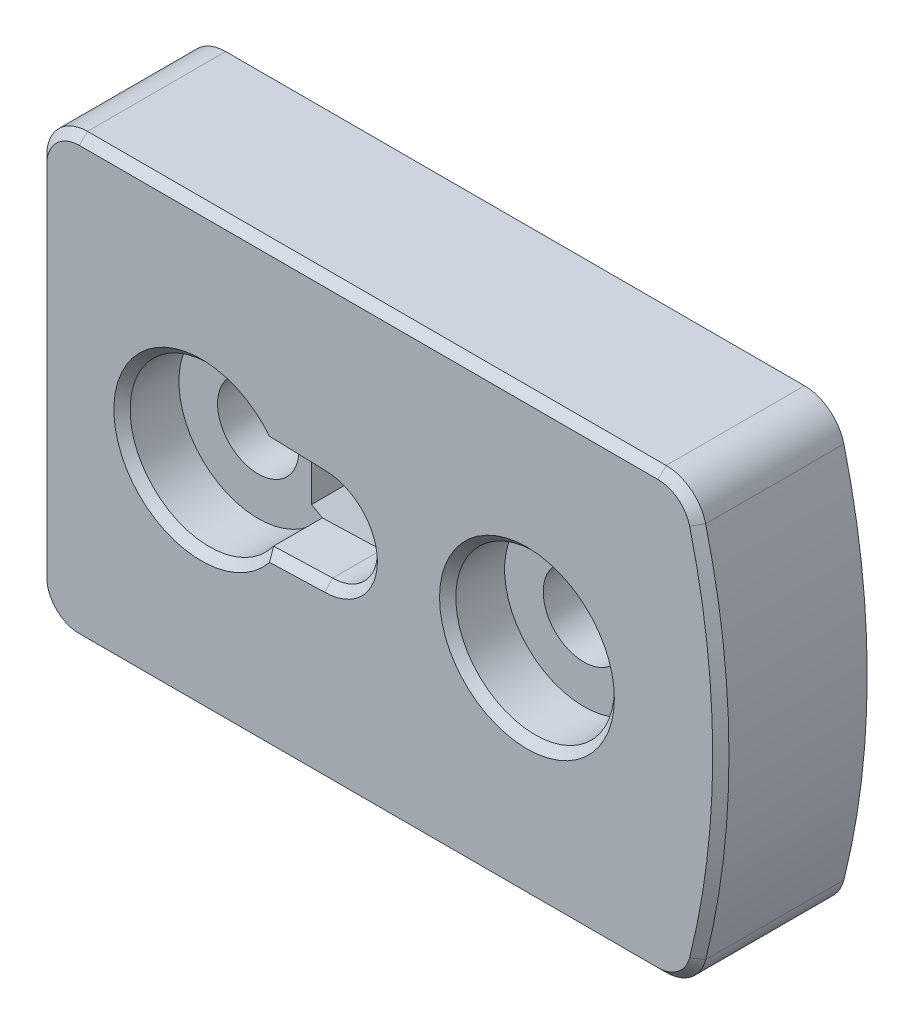
SolidWorks part; units mm, degrees
ref_plane "Front Plane" through (0, 0, 0) normal (0, 0, 1) x (1, 0, 0)
ref_plane "Top Plane" through (0, 0, 0) normal (0, 1, 0) x (1, 0, 0)
ref_plane "Right Plane" through (0, 0, 0) normal (1, 0, 0) x (0, 0, -1)
sketch "Sketch1" plane through (0, 0, 0) normal (0, 0, 1) x (1, 0, 0)
  line L0 (-10, 13.5) -> (-10, -13.5) construction
  line L1 (-20, -13.5) -> (20, -13.5)
  line L2 (-20, -13.5) -> (-20, 13.5)
  line L3 (-20, 13.5) -> (20, 13.5)
  line L5 (-20, -13.5) -> (20, 13.5) construction
  line L6 (-20, 13.5) -> (20, -13.5) construction
  line L7 (10.0266, 13.5) -> (10.0266, -13.5) construction
  line L8 (-8.92, 0) -> (-8.92, -38.6748) construction
  line L13 (-8.92, -38.6748) -> (-10.28, -38.6748) construction
  line L14 (-10.28, -38.6748) -> (-10.28, 0) construction
  line L15 (-2.42, 6.5) -> (43.4398, 6.5) construction
  line L16 (43.4398, 6.5) -> (43.4398, 7.86) construction
  line L17 (43.4398, 7.86) -> (-2.42, 7.86) construction
  line L18 (20, -13.5) -> (19.9199, -28.5934)
  circle A0 centre (-2.42, 0) radius 6.5
  arc A1 (-10.28, 0) -> (-2.42, 7.86) centre (-2.42, 0) cw construction
  arc A2 (20, 13.5) -> (20, -13.5) centre (-25.7558, 0) cw
  point P0 (-2.4466, -2.4466)
  point P7 (21.95, 0)
  dimension "D3" = 13
  dimension "D6" = 1.36
  dimension "D8" = 17.58
  dimension "D9" = 1.95
  dimension "D1" = 5.64
  dimension "D2" = 40
  dimension "D4" = 10
  dimension "D5" = 27
  dimension "D7" = 1.36
extrude "Boss-Extrude1" add sketch "Sketch1" along normal blind 9 contours L1 L3 L2 A0 | A0 region at (-19.5011, 0, 0) region at (-2.42, 0, 0)
sketch "Sketch2" plane through (0, 0, 9) normal (0, 0, 1) x (1, 0, 0)
  line L0 (-10, 13.5) -> (-10, -13.5) construction
  line L1 (10.0266, 13.5) -> (10.0266, -13.5) construction
  circle A0 centre (-10, 0) radius 2.5
  circle A1 centre (10.0266, 0) radius 2.5
  dimension "D1" = 5
extrude "Cut-Extrude1" cut sketch "Sketch2" against normal through all
sketch "Sketch3" plane through (0, 0, 9) normal (0, 0, 1) x (1, 0, 0)
  line L0 (-10, 13.5) -> (-10, -13.5) construction
  line L1 (10.0266, 13.5) -> (10.0266, -13.5) construction
  circle A0 centre (-10, 0) radius 4.875
  circle A1 centre (10.0266, 0) radius 4.875
  dimension "D1" = 9.75
extrude "Cut-Extrude2" cut sketch "Sketch3" against normal offset from surface (3.5 mm away) 5.5 up to face at (-7.5, 0, 0)
sketch "Sketch4" plane through (0, 0, 9) normal (0, 0, 1) x (1, 0, 0)
  circle A0 centre (-2.42, 0) radius 2.75
  dimension "D1" = 5.5
extrude "Cut-Extrude3" cut sketch "Sketch4" against normal through all
sketch "Sketch5" plane through (0, 0, 0) normal (0, 0, -1) x (-1, 0, 0)
  line L1 (6.72, -2.4826) -> (6.72, 2.4826)
  line L2 (6.72, 2.4826) -> (2.42, 4.9652)
  line L3 (2.42, 4.9652) -> (-1.88, 2.4826)
  line L4 (-1.88, 2.4826) -> (-1.88, -2.4826)
  line L5 (-1.88, -2.4826) -> (2.42, -4.9652)
  line L6 (2.42, -4.9652) -> (6.72, -2.4826)
  line L7 (20, -13.5) -> (20, 13.5) construction
  circle A0 centre (2.42, 0) radius 4.3 construction
  point P1 (2.42, 4.9652)
  dimension "D1" = 8.6
extrude "Cut-Extrude4" cut sketch "Sketch5" against normal up to surface (5.5 mm away) up to face at (-10.0225, 0, 5.5)
fillet "Fillet1" radius 2.5 4 edges at (-20, -13.5, 4.5) (-20, 13.5, 4.5) (20, -13.5, 4.5) (20, 13.5, 4.5)
chamfer "Chamfer1" distance 0.5 angle 45 8 edges at (0.2956, -13.5, 9) (-19.2678, -12.7678, 9) (-20, 0, 9) (-19.2678, 12.7678, 9) (0.2956, 13.5, 9) (19.629, -12.9711, 9) (21.95, 0, 9) (19.629, 12.9711, 9)
sketch "Sketch6" plane through (0, 0, 9) normal (0, 0, 1) x (1, 0, 0)
  line L5 (-6.0563, 2.8658) -> (-2.42, 2.75)
  line L6 (-6.0563, -2.8658) -> (-2.42, -2.75)
  line L7 (-6.0563, 2.8658) -> (-2.42, 4.9652) construction
  line L9 (-6.0563, -2.8658) -> (-6.72, -2.4826)
  line L12 (-6.72, 2.4826) -> (-2.42, 4.9652) construction
  line L13 (-6.72, -2.4826) -> (-6.72, 2.4826)
  line L19 (-6.72, 2.4826) -> (-6.0563, 2.8658)
  arc A0 (-5.1412, -0.397) -> (-5.1412, 0.397) centre (-2.42, 0) ccw construction
  arc A1 (-6.0563, 2.8658) -> (-6.0563, -2.8658) centre (-10, 0) ccw construction
  arc A2 (-2.42, -2.75) -> (-2.42, 2.75) centre (-2.42, 0) ccw
  arc A4 (-5.1412, 0.397) -> (-5.1412, -0.397) centre (-10, 0) ccw construction
  point P10 (-2.42, -2.75)
  point P11 (-1.6646, -2.6442)
  point P14 (-6.0521, 2.8682)
  point P17 (-6.72, -2.4826)
extrude "Cut-Extrude5" cut sketch "Sketch6" against normal through all and the other way through all
fillet "Fillet2" [suppressed] radius 3
chamfer "Chamfer3" distance 0.5 angle 45 5 edges at (14.9016, 0, 9) (-4.2381, -2.8079, 9) (0.33, 0, 9) (-4.2381, 2.8079, 9) (-14.875, 0, 9)
